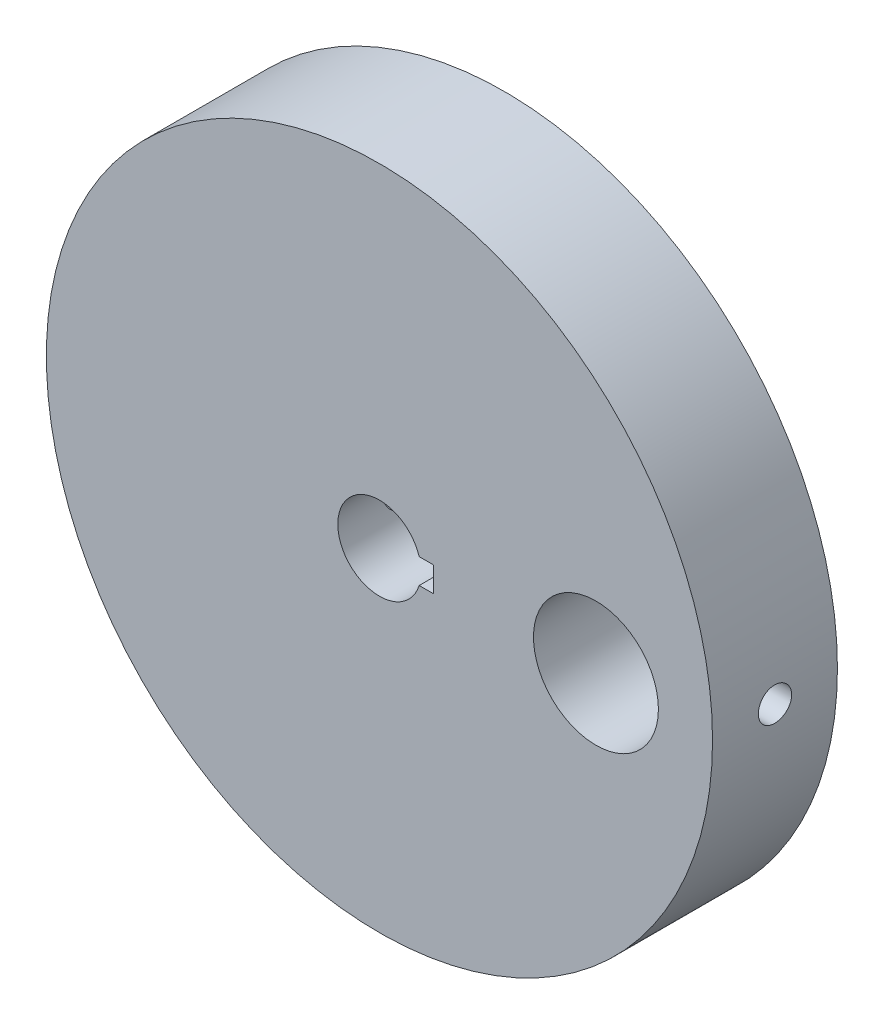
SolidWorks part; units mm, degrees
material "Plain Carbon Steel"
ref_plane "Front Plane" through (0, 0, 0) normal (0, 0, 1) x (1, 0, 0)
ref_plane "Top Plane" through (0, 0, 0) normal (0, 1, 0) x (1, 0, 0)
ref_plane "Right Plane" through (0, 0, 0) normal (1, 0, 0) x (0, 0, -1)
sketch "Sketch1" plane through (0, 0, 0) normal (0, 0, 1) x (1, 0, 0)
  line L2 (4.7697, 1.5) -> (6.5, 1.5)
  line L4 (4.7697, -1.5) -> (6.5, -1.5)
  line L5 (6.5, 1.5) -> (6.5, -1.5)
  line L6 (3.5, 1.5) -> (6.5, -1.5) construction
  line L7 (3.5, -1.5) -> (6.5, 1.5) construction
  circle A0 centre (0, 0) radius 40
  arc A1 (4.7697, 1.5) -> (4.7697, -1.5) centre (0, 0) ccw
  circle A2 centre (26, 0) radius 7.5
  point P3 (0, 0)
  point P8 (6.5, 0)
  point P9 (5, 0)
  dimension "D1" = 80
  dimension "D2" = 10
  dimension "D3" = 15
  dimension "D4" = 26
  dimension "D5" = 3
  dimension "D6" = 1.5
extrude "Boss-Extrude1" add sketch "Sketch1" along normal mid plane 15
sketch "Sketch2" plane through (0, 0, 0) normal (1, 0, 0) x (0, 0, -1)
  circle A0 centre (0, 0) radius 2
  dimension "D1" = 4
extrude "Cut-Extrude1" cut sketch "Sketch2" against normal up to next
cosmetic thread "Cosmetic Thread2" parameters "D2"=5
extrude "Cut-Extrude2" cut sketch "Sketch2<2>" against normal up to next from offset 40
sketch "Sketch2<2>" plane through (0, 0, 0) normal (1, 0, 0) x (0, 0, -1) same geometry as "Sketch2"
cosmetic thread "Cosmetic Thread1" parameters "D2"=5
